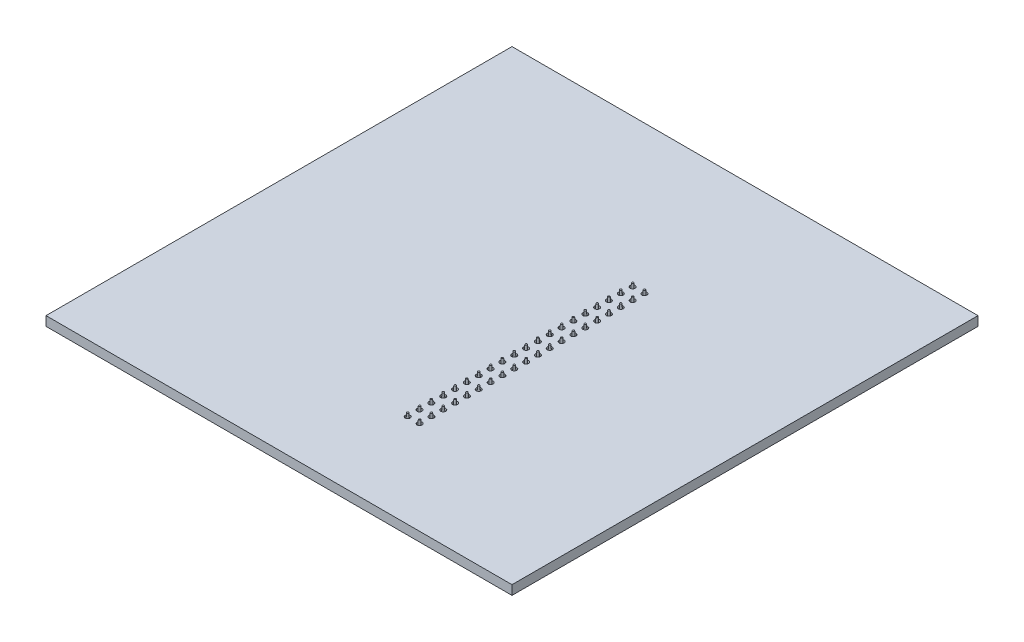
SolidWorks part; units mm, degrees
ref_plane "Front Plane" through (0, 0, 0) normal (0, 0, 1) x (1, 0, 0)
ref_plane "Top Plane" through (0, 0, 0) normal (0, 1, 0) x (1, 0, 0)
ref_plane "Right Plane" through (0, 0, 0) normal (1, 0, 0) x (0, 0, -1)
sketch "Sketch1" plane through (0, 0, 0) normal (0, 1, 0) x (1, 0, 0)
  line L1 (-50, -50) -> (50, -50)
  line L2 (-50, -50) -> (-50, 50)
  line L3 (-50, 50) -> (50, 50)
  line L4 (50, -50) -> (50, 50)
  line L5 (-50, -50) -> (50, 50) construction
  line L6 (-50, 50) -> (50, -50) construction
  point P0 (0, 0)
  dimension "D1" = 100
  dimension "D2" = 100
extrude "Boss-Extrude1" add sketch "Sketch1" along normal blind 2
sketch "Sketch2" plane through (0, 2, 0) normal (0, 1, 0) x (1, 0, 0)
  line L0 (10.138, -29.974) -> (10.138, -27.434) construction
  circle A0 centre (10.138, -29.974) radius 0.535
  circle A1 centre (7.598, -29.974) radius 0.535
  circle A2 centre (7.598, -27.434) radius 0.535
  circle A3 centre (7.598, -24.894) radius 0.535
  circle A4 centre (7.598, -22.354) radius 0.535
  circle A5 centre (7.598, -19.814) radius 0.535
  circle A6 centre (7.598, -17.274) radius 0.535
  circle A7 centre (7.598, -14.734) radius 0.535
  circle A8 centre (7.598, -12.194) radius 0.535
  circle A9 centre (7.598, -9.654) radius 0.535
  circle A10 centre (7.598, -7.114) radius 0.535
  circle A11 centre (7.598, -4.574) radius 0.535
  circle A12 centre (7.598, -2.034) radius 0.535
  circle A13 centre (7.598, 0.506) radius 0.535
  circle A14 centre (7.598, 3.046) radius 0.535
  circle A15 centre (7.598, 5.586) radius 0.535
  circle A16 centre (7.598, 8.126) radius 0.535
  circle A17 centre (7.598, 10.666) radius 0.535
  circle A18 centre (7.598, 13.206) radius 0.535
  circle A19 centre (7.598, 15.746) radius 0.535
  circle A20 centre (7.598, 18.286) radius 0.535
  circle A21 centre (10.138, -27.434) radius 0.535
  circle A22 centre (10.138, -24.894) radius 0.535
  circle A23 centre (10.138, -22.354) radius 0.535
  circle A24 centre (10.138, -19.814) radius 0.535
  circle A25 centre (10.138, -17.274) radius 0.535
  circle A26 centre (10.138, -14.734) radius 0.535
  circle A27 centre (10.138, -12.194) radius 0.535
  circle A28 centre (10.138, -9.654) radius 0.535
  circle A29 centre (10.138, -7.114) radius 0.535
  circle A30 centre (10.138, -4.574) radius 0.535
  circle A31 centre (10.138, -2.034) radius 0.535
  circle A32 centre (10.138, 0.506) radius 0.535
  circle A33 centre (10.138, 3.046) radius 0.535
  circle A34 centre (10.138, 5.586) radius 0.535
  circle A35 centre (10.138, 8.126) radius 0.535
  circle A36 centre (10.138, 10.666) radius 0.535
  circle A37 centre (10.138, 13.206) radius 0.535
  circle A38 centre (10.138, 15.746) radius 0.535
  circle A39 centre (10.138, 18.286) radius 0.535
  dimension "D1" = 1.07
  dimension "D2" = 39.862
  dimension "D3" = 20.026
  dimension "D6" = 2.54
  dimension "D4" = 2
  dimension "D5" = 20
extrude "Cut-Extrude1" cut sketch "Sketch2" against normal through all
ref_plane "Plane1" through (0, -5, 0) normal (0, -1, 0) x (-1, 0, 0)
sketch "Sketch4" plane through (0, -5, 0) normal (0, 1, 0) x (1, 0, 0)
  line L0 (9.368, -29.204) -> (10.908, -29.204)
  line L1 (8.868, -31.244) -> (11.408, -31.244)
  line L2 (8.868, -31.244) -> (8.868, -28.704)
  line L3 (8.868, -28.704) -> (11.408, -28.704)
  line L4 (11.408, -31.244) -> (11.408, -28.704)
  line L5 (8.868, -31.244) -> (11.408, -28.704) construction
  line L6 (8.868, -28.704) -> (11.408, -31.244) construction
  line L7 (10.908, -30.744) -> (10.908, -29.204)
  line L8 (9.368, -30.744) -> (10.908, -30.744)
  line L9 (9.368, -30.744) -> (9.368, -29.204)
  point P0 (10.138, -29.974)
  dimension "D1" = 2.54
  dimension "D2" = 2.54
  dimension "D3" = 0.5
extrude "Boss-Extrude2" add sketch "Sketch4" against normal blind 8.4
pattern_linear "LPattern2" count 20 spacing 2.54 along (0, 0, -1) count 2 spacing 2.54 along (-1, 0, 0) of "Boss-Extrude2"
sketch "Sketch5" plane through (0, -5, 0) normal (0, -1, 0) x (-1, 0, 0)
  circle A0 centre (-7.598, 3.046) radius 0.535 construction
  circle A1 centre (-7.598, 5.586) radius 0.535 construction
  circle A2 centre (-7.598, 8.126) radius 0.535 construction
  circle A3 centre (-7.598, 10.666) radius 0.535 construction
  circle A4 centre (-7.598, 13.206) radius 0.535 construction
  circle A5 centre (-7.598, 15.746) radius 0.535 construction
  circle A6 centre (-7.598, 18.286) radius 0.535 construction
  circle A7 centre (-10.138, 18.286) radius 0.535 construction
  circle A8 centre (-10.138, 15.746) radius 0.535 construction
  circle A9 centre (-10.138, 13.206) radius 0.535 construction
  circle A10 centre (-10.138, 10.666) radius 0.535 construction
  circle A11 centre (-10.138, 8.126) radius 0.535 construction
  circle A12 centre (-10.138, 5.586) radius 0.535 construction
  circle A13 centre (-10.138, 3.046) radius 0.535 construction
  circle A14 centre (-7.598, 0.506) radius 0.535 construction
  circle A15 centre (-10.138, 0.506) radius 0.535 construction
  circle A16 centre (-10.138, -2.034) radius 0.535 construction
  circle A17 centre (-7.598, -2.034) radius 0.535 construction
  circle A18 centre (-7.598, -4.574) radius 0.535 construction
  circle A19 centre (-10.138, -4.574) radius 0.535 construction
  circle A20 centre (-10.138, -7.114) radius 0.535 construction
  circle A21 centre (-7.598, -7.114) radius 0.535 construction
  circle A22 centre (-7.598, -9.654) radius 0.535 construction
  circle A23 centre (-10.138, -9.654) radius 0.535 construction
  circle A24 centre (-7.598, -12.194) radius 0.535 construction
  circle A25 centre (-10.138, -12.194) radius 0.535 construction
  circle A26 centre (-10.138, -14.734) radius 0.535 construction
  circle A27 centre (-7.598, -14.734) radius 0.535 construction
  circle A28 centre (-7.598, -17.274) radius 0.535 construction
  circle A29 centre (-10.138, -17.274) radius 0.535 construction
  circle A30 centre (-10.138, -19.814) radius 0.535 construction
  circle A31 centre (-7.598, -19.814) radius 0.535 construction
  circle A32 centre (-7.598, -22.354) radius 0.535 construction
  circle A33 centre (-10.138, -22.354) radius 0.535 construction
  circle A34 centre (-7.598, -24.894) radius 0.535 construction
  circle A35 centre (-10.138, -24.894) radius 0.535 construction
  circle A36 centre (-7.598, -27.434) radius 0.535 construction
  circle A37 centre (-10.138, -27.434) radius 0.535 construction
  circle A38 centre (-10.138, -29.974) radius 0.535 construction
  circle A39 centre (-7.598, -29.974) radius 0.535 construction
  circle A40 centre (-7.598, 3.046) radius 0.535
  circle A41 centre (-7.598, 5.586) radius 0.535
  circle A42 centre (-7.598, 8.126) radius 0.535
  circle A43 centre (-7.598, 10.666) radius 0.535
  circle A44 centre (-7.598, 13.206) radius 0.535
  circle A45 centre (-7.598, 15.746) radius 0.535
  circle A46 centre (-7.598, 18.286) radius 0.535
  circle A47 centre (-10.138, 18.286) radius 0.535
  circle A48 centre (-10.138, 15.746) radius 0.535
  circle A49 centre (-10.138, 13.206) radius 0.535
  circle A50 centre (-10.138, 10.666) radius 0.535
  circle A51 centre (-10.138, 8.126) radius 0.535
  circle A52 centre (-10.138, 5.586) radius 0.535
  circle A53 centre (-10.138, 3.046) radius 0.535
  circle A54 centre (-7.598, 0.506) radius 0.535
  circle A55 centre (-10.138, 0.506) radius 0.535
  circle A56 centre (-10.138, -2.034) radius 0.535
  circle A57 centre (-7.598, -2.034) radius 0.535
  circle A58 centre (-7.598, -4.574) radius 0.535
  circle A59 centre (-10.138, -4.574) radius 0.535
  circle A60 centre (-10.138, -7.114) radius 0.535
  circle A61 centre (-7.598, -7.114) radius 0.535
  circle A62 centre (-7.598, -9.654) radius 0.535
  circle A63 centre (-10.138, -9.654) radius 0.535
  circle A64 centre (-7.598, -12.194) radius 0.535
  circle A65 centre (-10.138, -12.194) radius 0.535
  circle A66 centre (-10.138, -14.734) radius 0.535
  circle A67 centre (-7.598, -14.734) radius 0.535
  circle A68 centre (-7.598, -17.274) radius 0.535
  circle A69 centre (-10.138, -17.274) radius 0.535
  circle A70 centre (-10.138, -19.814) radius 0.535
  circle A71 centre (-7.598, -19.814) radius 0.535
  circle A72 centre (-7.598, -22.354) radius 0.535
  circle A73 centre (-10.138, -22.354) radius 0.535
  circle A74 centre (-7.598, -24.894) radius 0.535
  circle A75 centre (-10.138, -24.894) radius 0.535
  circle A76 centre (-7.598, -27.434) radius 0.535
  circle A77 centre (-10.138, -27.434) radius 0.535
  circle A78 centre (-10.138, -29.974) radius 0.535
  circle A79 centre (-7.598, -29.974) radius 0.535
extrude "Boss-Extrude3" add sketch "Sketch5" against normal blind 7.75 draft 2.5 separate body
